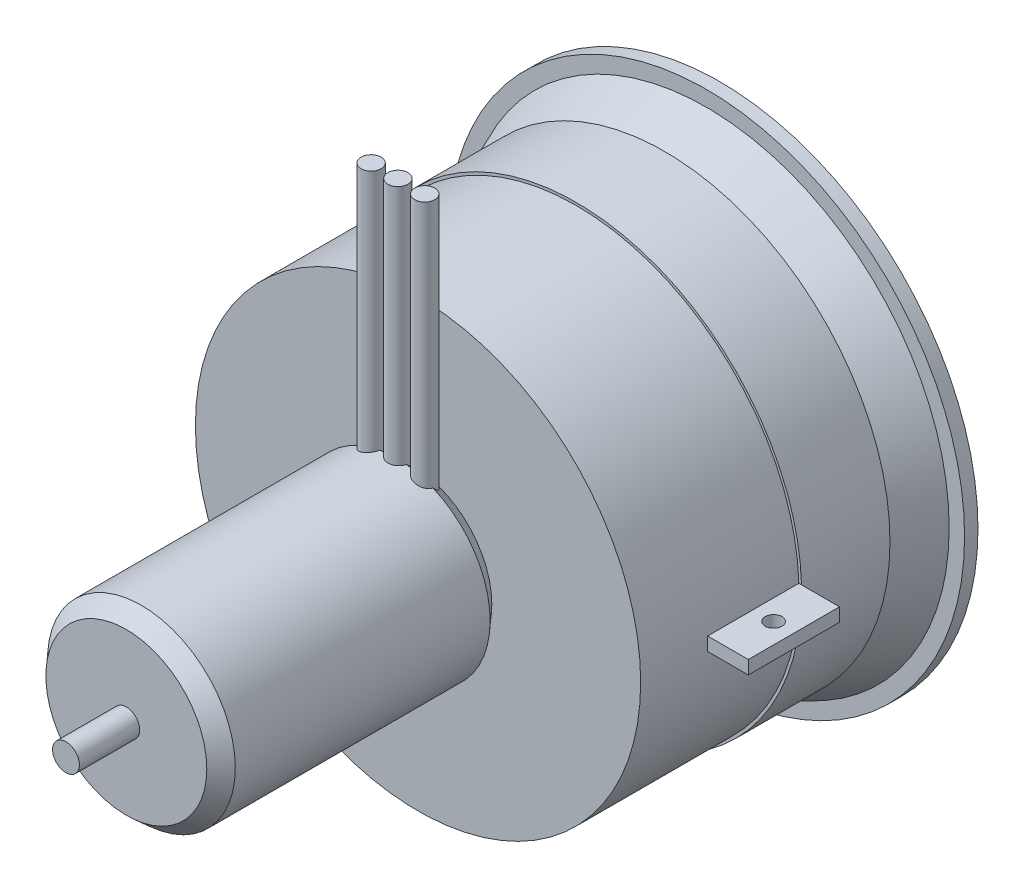
SolidWorks part; units mm, degrees
ref_plane "Front Plane" through (0, 0, 0) normal (1, 0, 0) x (0, 1, 0)
ref_plane "Top Plane" through (0, 0, 0) normal (0, 0, 1) x (0, 1, 0)
ref_plane "Right Plane" through (0, 0, 0) normal (0, 1, 0) x (-1, 0, 0)
sketch "Sketch1" plane through (0, 0, 0) normal (1, 0, 0) x (0, 1, 0)
  line L0 (0, 0) -> (0, -32.442) construction
  line L1 (0, 0) -> (38.5, 0)
  line L2 (38.5, 0) -> (38.5, 2)
  line L3 (38.5, 2) -> (36.2, 2)
  line L4 (36.2, 2) -> (33.6, 8.225)
  line L5 (33.6, 8.225) -> (33.6, 21.4)
  line L6 (33.2, 21.4) -> (33.2, 45)
  line L7 (33.2, 45) -> (5, 45)
  line L9 (5, 46) -> (12, 46)
  line L10 (12, 46) -> (14, 48.25)
  line L11 (14, 48.25) -> (14, 86.25)
  line L12 (14, 86.25) -> (12, 88.5)
  line L13 (12, 88.5) -> (2, 88.5)
  line L14 (2, 88.5) -> (2, 97.5)
  line L15 (2, 97.5) -> (0, 97.5)
  line L17 (33.2, 21.4) -> (33.6, 21.4)
  line L19 (0, 97.5) -> (0, 0)
  line L20 (5, 46) -> (5, 45)
  point P11 (14, 78.6456)
  point P12 (4.3523, 45)
  point P20 (14, 49.8597)
  point P21 (14, 76.3054)
  point P23 (0, 0)
  point P24 (0, 0)
  point P25 (0, 0)
  point P26 (0, 0)
  point P27 (0, 0)
  point P28 (11.5089, 88.5)
  point P29 (0, 0)
  dimension "D1" = 77
  dimension "D2" = 72.4
  dimension "D3" = 67.2
  dimension "D4" = 66.4
  dimension "D5" = 45
  dimension "D6" = 23.6
  dimension "D7" = 97.5
  dimension "D8" = 2
  dimension "D9" = 4
  dimension "D10" = 28
  dimension "D11" = 1
  dimension "D12" = 42.5
  dimension "D13" = 10
  dimension "D14" = 10
  dimension "D15" = 38
revolve "Revolve1" add sketch "Sketch1" angle 360 about L0
sketch "Sketch3" plane through (0, 0, 0) normal (1, 0, 0) x (0, 1, 0)
  line L0 (33.2, 45) -> (-33.2, 45) construction
  line L1 (-1, 35) -> (1, 35)
  line L2 (-1, 35) -> (-1, 21.4)
  line L3 (-1, 21.4) -> (1, 21.4)
  line L4 (1, 35) -> (1, 21.4)
  point P4 (0, 21.4)
  point P8 (3.3597, 21.4)
  dimension "D1" = 13.6
  dimension "D2" = 10
  dimension "D3" = 2
extrude "Boss-Extrude1" add sketch "Sketch3" along normal mid plane 78.5
sketch "Sketch4" plane through (0, 1, 0) normal (0, 1, 0) x (-1, 0, 0)
  line L0 (-39.25, 35) -> (-33.1849, 35) construction
  line L1 (-39.25, 28.2) -> (-33.1849, 28.2) construction
  line L4 (-39.25, 21.4) -> (-39.25, 35) construction
  line L5 (-33.1849, 21.4) -> (-33.1849, 35) construction
  circle A0 centre (-36.2175, 28.2) radius 1.25
  point P4 (0, 0)
  dimension "D2" = 2.5
  dimension "D1" = 6.8
extrude "Cut-Extrude1" cut sketch "Sketch4" against normal through all
mirror "Mirror1" about plane through (0, 0, 0) normal (1, 0, 0) of "Cut-Extrude1"
sketch "Sketch5" plane through (0, 0, 0) normal (0, 1, 0) x (-1, 0, 0)
  line L2 (-12, 46) -> (12, 46) construction
  circle A0 centre (0, 48) radius 1.5
  circle A1 centre (4, 48) radius 1.5
  circle A2 centre (-4, 48) radius 1.5
  point P6 (0, 49.2019)
  point P7 (0, 0)
  point P8 (0.5926, 50.1481)
  point P11 (0, 0)
  point P13 (3.4812, 48)
  point P14 (-3.3732, 48)
  dimension "D1" = 3
  dimension "D2" = 0.5
  dimension "D3" = 1
  dimension "D4" = 1
extrude "Boss-Extrude5" add sketch "Sketch5" along normal blind 50
